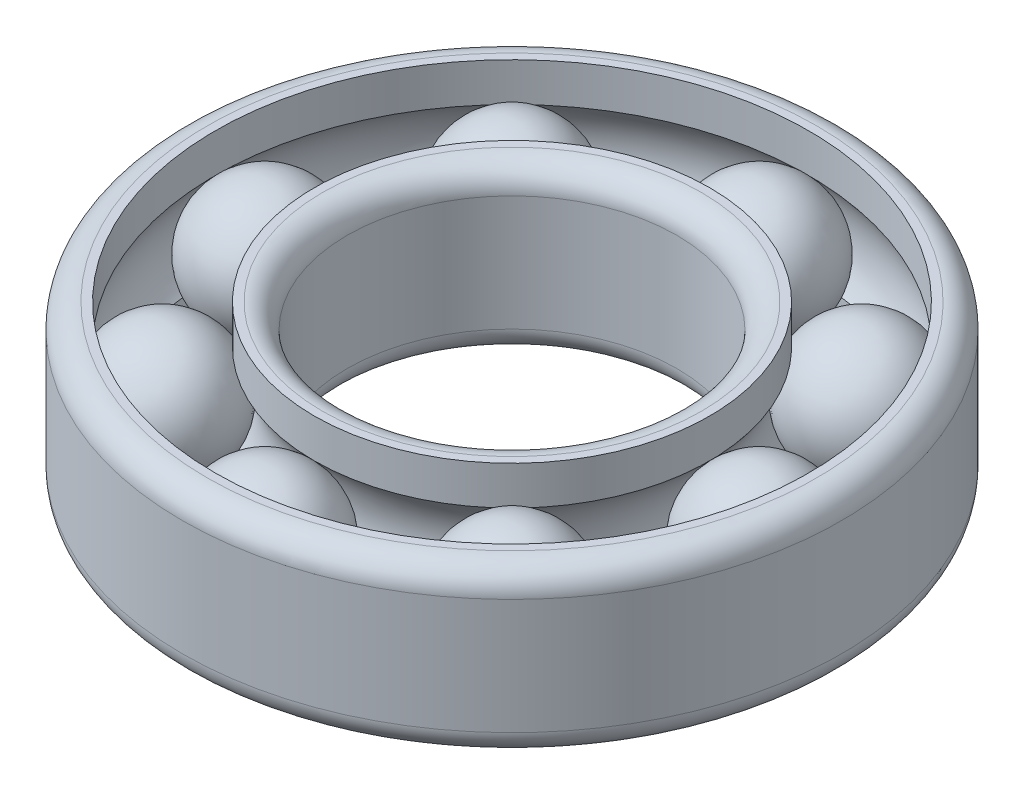
SolidWorks part; units mm, degrees
ref_plane "Front Plane" through (0, 0, 0) normal (0, 0, 1) x (1, 0, 0)
ref_plane "Top Plane" through (0, 0, 0) normal (0, 1, 0) x (1, 0, 0)
ref_plane "Right Plane" through (0, 0, 0) normal (1, 0, 0) x (0, 0, -1)
sketch "Sketch1" plane through (0, 0, 0) normal (0, 0, 1) x (1, 0, 0)
  line L0 (-2, -0.5) -> (-1.8, -0.3) construction
  line L1 (-1.2, 0.5) -> (-1, 0.5)
  line L2 (-1.2, 0.5) -> (-1.2, 0.2646)
  line L3 (-1.2, -0.5) -> (-1, -0.5)
  line L4 (-1, 0.5) -> (-1, -0.5)
  line L5 (-1.2, 0.5) -> (-1, -0.5) construction
  line L6 (-1.2, -0.5) -> (-1, 0.5) construction
  line L7 (-2, 0.5) -> (-1.8, 0.5)
  line L8 (-2, 0.5) -> (-2, -0.5)
  line L9 (-2, -0.5) -> (-1.8, -0.5)
  line L10 (-1.8, 0.5) -> (-1.8, 0.2646)
  line L11 (-2, 0.5) -> (-1.8, -0.5) construction
  line L12 (-2, -0.5) -> (-1.8, 0.5) construction
  line L13 (-1.2, 0.3) -> (-1, 0.5) construction
  line L14 (-1.8, -0.2646) -> (-1.8, -0.5)
  line L15 (-1.2, -0.2646) -> (-1.2, -0.5)
  line L16 (-1, 0.5) -> (-2, -0.5) construction
  line L18 (-1.5, 0.4) -> (-1.5, -0.4)
  arc A0 (-1.8, 0.2646) -> (-1.8, -0.2646) centre (-1.5, 0) ccw
  arc A1 (-1.2, -0.2646) -> (-1.2, 0.2646) centre (-1.5, 0) ccw
  arc A2 (-1.5, 0.4) -> (-1.5, -0.4) centre (-1.5, 0) cw
  point P0 (-1.1, 0)
  point P5 (-1.9, 0)
  dimension "D5" = 0.4
  dimension "D1" = 1
  dimension "D2" = 0.2
  dimension "D3" = 1
  dimension "D4" = 2
  dimension "D6" = 0.8
revolve "Revolve1" add sketch "Sketch1" angle 360 about L18 region at (-1.3302, 0, 0)
ref_axis "Axis1" through (0, 0.55, 0) along (0, -1, 0)
revolve "Revolve2" add sketch "Sketch1<3>" angle 360 about axis through (0, 0.55, 0) along (0, -1, 0) region at (-1.0868, 0, 0) region at (-1.9132, 0, 0)
sketch "Sketch1<3>" plane through (0, 0, 0) normal (0, 0, 1) x (1, 0, 0) same geometry as "Sketch1"
fillet "Fillet1" radius 0.15 2 edges at (0, 0.5, 2) (0, -0.5, 2)
fillet "Fillet2" radius 0.15 2 edges at (0, 0.5, 1) (0, -0.5, 1)
pattern_circular "CirPattern3" count 8 over 360 about axis through (0, 0.55, 0) along (0, -1, 0) of "Revolve1"
